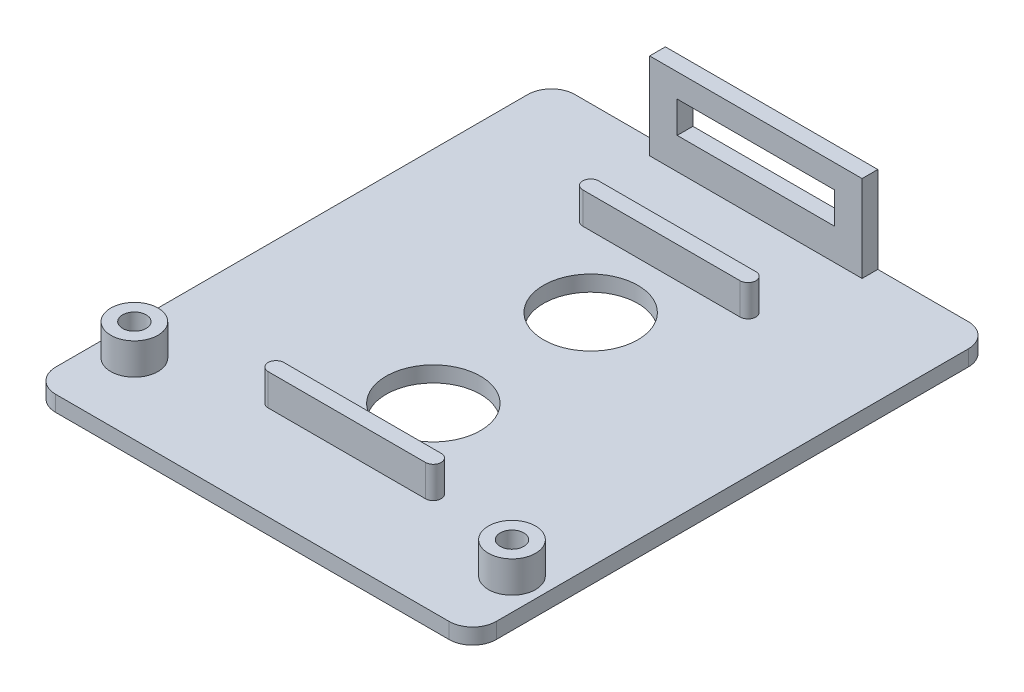
SolidWorks part; units mm, degrees
ref_plane "Front Plane" through (0, 0, 0) normal (0, 0, 1) x (1, 0, 0)
ref_plane "Top Plane" through (0, 0, 0) normal (0, 1, 0) x (1, 0, 0)
ref_plane "Right Plane" through (0, 0, 0) normal (1, 0, 0) x (0, 0, -1)
sketch "Base" plane through (0, 0, 0) normal (0, 1, 0) x (1, 0, 0)
  line L0 (-5, -10) -> (5, -10) construction
  line L1 (12.5, 16.5) -> (-12.5, 16.5)
  line L2 (14, 15) -> (14, -15)
  line L3 (12.5, -16.5) -> (-12.5, -16.5)
  line L4 (-14, 15) -> (-14, -15)
  line L11 (-5, -9.5) -> (5, -9.5)
  line L12 (-5, -10.5) -> (5, -10.5)
  line L13 (-5, 10) -> (5, 10) construction
  line L14 (-6.75, 16.5) -> (6.75, 16.5)
  line L15 (-6.75, 16.5) -> (-6.75, 15.5)
  line L16 (-6.75, 15.5) -> (6.75, 15.5)
  line L17 (6.75, 16.5) -> (6.75, 15.5)
  line L18 (-5, 10.5) -> (5, 10.5)
  line L19 (-5, 9.5) -> (5, 9.5)
  arc A0 (-12.5, 16.5) -> (-14, 15) centre (-12.5, 15) ccw
  arc A1 (14, 15) -> (12.5, 16.5) centre (12.5, 15) ccw
  arc A2 (-12.5, -16.5) -> (-14, -15) centre (-12.5, -15) cw
  arc A3 (14, -15) -> (12.5, -16.5) centre (12.5, -15) cw
  circle A4 centre (-12, -12) radius 1.5
  circle A5 centre (-12, -12) radius 0.75
  circle A6 centre (12, -12) radius 1.5
  circle A7 centre (12, -12) radius 0.75
  arc A8 (-5, -9.5) -> (-5, -10.5) centre (-5, -10) ccw
  arc A9 (5, -10.5) -> (5, -9.5) centre (5, -10) ccw
  arc A10 (-5, 10.5) -> (-5, 9.5) centre (-5, 10) ccw
  arc A11 (5, 9.5) -> (5, 10.5) centre (5, 10) ccw
  circle A12 centre (0, 5) radius 3
  circle A13 centre (0, -5) radius 3
  point P4 (-12, -12)
  point P21 (12, -12)
  point P33 (0, -10)
  point P42 (0, 10)
sketch "PCB holder" plane through (0, 0, 0) normal (0, 1, 0) x (1, 0, 0)
  line L0 (-10, -10.5) -> (-12, -10.5)
  line L1 (9, 15.5) -> (-9, 15.5)
  line L2 (10, 14.5) -> (10, -14.5)
  line L3 (9, -15.5) -> (-9, -15.5)
  line L4 (-10, 14.5) -> (-10, -14.5)
  line L5 (-12, -13.5) -> (-10, -13.5)
  line L6 (12, -10.5) -> (10, -10.5)
  line L7 (8.75, 14.75) -> (-8.75, 14.75)
  line L8 (9.25, 14.25) -> (9.25, -14.25)
  line L9 (8.75, -14.75) -> (-8.75, -14.75)
  line L10 (-9.25, 14.25) -> (-9.25, -14.25)
  line L11 (12, -13.5) -> (10, -13.5)
  line L13 (-4.75, 15.5) -> (4.75, 15.5)
  line L14 (-4.75, 15.5) -> (-4.75, 16.75)
  line L15 (-4.75, 16.75) -> (4.75, 16.75)
  line L16 (4.75, 15.5) -> (4.75, 16.75)
  arc A0 (-9.25, 14.25) -> (-8.75, 14.75) centre (-8.75, 14.25) cw
  arc A1 (9.25, 14.25) -> (8.75, 14.75) centre (8.75, 14.25) ccw
  arc A2 (8.75, -14.75) -> (9.25, -14.25) centre (8.75, -14.25) ccw
  arc A3 (-9.25, -14.25) -> (-8.75, -14.75) centre (-8.75, -14.25) ccw
  arc A4 (-9, 15.5) -> (-10, 14.5) centre (-9, 14.5) ccw
  arc A5 (9, 15.5) -> (10, 14.5) centre (9, 14.5) cw
  arc A6 (-10, -14.5) -> (-9, -15.5) centre (-9, -14.5) ccw
  arc A7 (10, -14.5) -> (9, -15.5) centre (9, -14.5) cw
  arc A8 (-12, -10.5) -> (-12, -13.5) centre (-12, -12) ccw
  arc A9 (12, -10.5) -> (12, -13.5) centre (12, -12) cw
  circle A10 centre (-12, -12) radius 0.75
  circle A11 centre (12, -12) radius 0.75
  circle A12 centre (0, 5) radius 3
  circle A13 centre (0, -5) radius 3
  point P0 (0, 0)
  point P1 (0, 0)
  point P7 (0, 0)
  line B0 (-8.5, 14.5) -> (8.5, 14.5) construction
  line B1 (-9, 14) -> (-9, -14) construction
  line B2 (-8.5, -14.5) -> (8.5, -14.5) construction
  line B3 (9, 14) -> (9, -14) construction
  arc B4 (-9, 14) -> (-8.5, 14.5) centre (-8.5, 14) cw construction
  arc B5 (9, 14) -> (8.5, 14.5) centre (8.5, 14) ccw construction
  arc B6 (8.5, -14.5) -> (9, -14) centre (8.5, -14) ccw construction
  arc B7 (-9, -14) -> (-8.5, -14.5) centre (-8.5, -14) ccw construction
sketch_block_instance "Block2-1"
sketch_block "Block2"
extrude "Boss-Extrude5" add sketch "Base<4>" along normal blind 3 contours A4 A5 | A6 A7 region at (-13.4576, 0, 12) region at (10.5424, 0, 12)
sketch "Base<4>" plane through (0, 0, 0) normal (0, 1, 0) x (1, 0, 0) same geometry as "Base"
extrude "Boss-Extrude7" add sketch "Base" along normal blind 6.5 contours L17 L1 L15 L16 region at (0, 0, -16)
extrude "Boss-Extrude8" add sketch "Base<7>" along normal blind 1 contours A3 L2 A1 L1 L17 L16 L15 A0 L4 A2 L3 A13 A12 A11 L19 A10 L18 A9 L12 A8 L11 A6 A4 | L19 A11 L18 A10 | L12 A9 L11 A8 region at (0, 0, 0.0568)
sketch "Base<7>" plane through (0, 0, 0) normal (0, 1, 0) x (1, 0, 0) same geometry as "Base"
extrude "Boss-Extrude9" add sketch "Base<8>" along normal blind 3 contours L19 A11 L18 A10 | L11 A9 L12 A8
sketch "Base<8>" plane through (0, 0, 0) normal (0, 1, 0) x (1, 0, 0) same geometry as "Base"
sketch "slit" plane through (0, 0, -15.5) normal (0, 0, 1) x (1, 0, 0)
  line L1 (-5, 5) -> (5, 5)
  line L2 (-5, 5) -> (-5, 3)
  line L3 (-5, 3) -> (5, 3)
  line L4 (5, 5) -> (5, 3)
extrude "Cut-Extrude2" cut sketch "slit" against normal blind 6.5
